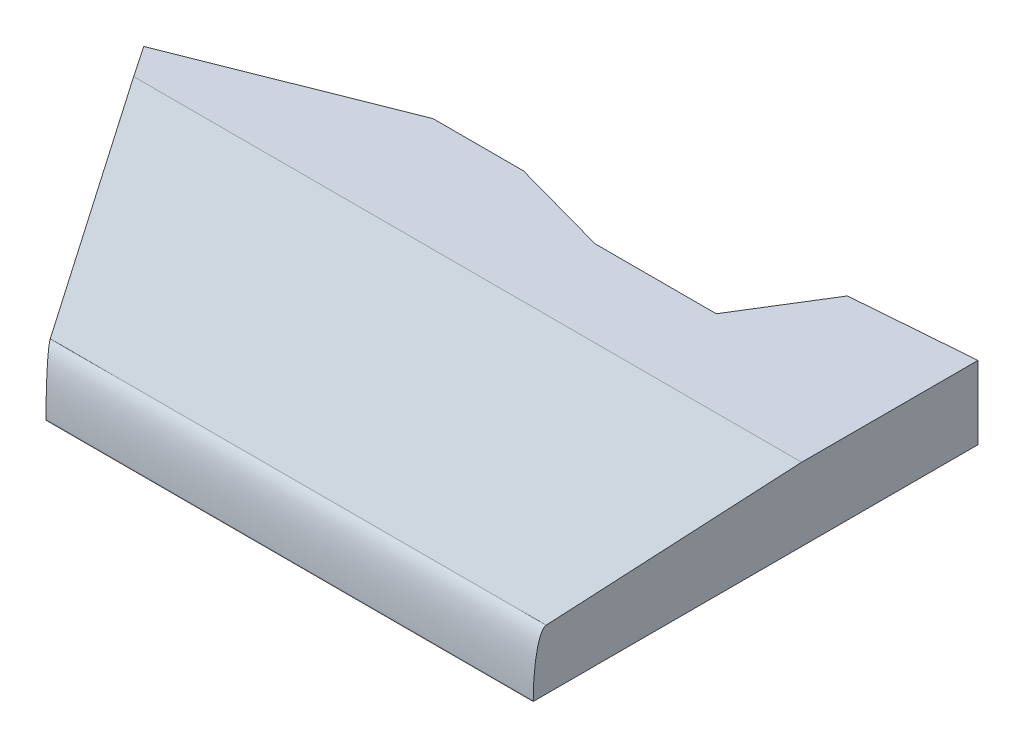
SolidWorks part; units mm, degrees
ref_plane "Front Plane" through (0, 0, 0) normal (0, 0, 1) x (1, 0, 0)
ref_plane "Top Plane" through (0, 0, 0) normal (0, 1, 0) x (1, 0, 0)
ref_plane "Right Plane" through (0, 0, 0) normal (1, 0, 0) x (0, 0, -1)
sketch "outline" plane through (0, 0, 0) normal (0, 1, 0) x (1, 0, 0)
  line L0 (23.1521, 111.8179) -> (23.1521, 32.6746) construction
  line L1 (23.1521, 32.6746) -> (26.0432, 26.4778) construction
  line L2 (26.0432, 26.4778) -> (40.0838, 2.1711) construction
  line L3 (40.0838, 2.1711) -> (75.1374, 16.0801) construction
  line L4 (75.1374, 16.0801) -> (93.8189, 16.0801) construction
  line L5 (93.8189, 16.0801) -> (112.2703, 10.9819) construction
  line L6 (112.2703, 10.9819) -> (130.9633, 10.9819) construction
  line L7 (130.9633, 10.9819) -> (140.1644, 25.8373) construction
  line L8 (140.1644, 25.8373) -> (160.3881, 27.4157) construction
  line L9 (160.3881, 27.4157) -> (160.3881, 105.6539) construction
  line L10 (160.3881, 105.6539) -> (121.5662, 111.8179) construction
  line L11 (121.5662, 111.8179) -> (23.1521, 111.8179) construction
  line L12 (22.7521, 112.2179) -> (22.7521, 32.5858)
  line L13 (22.7521, 32.5858) -> (25.6881, 26.2928)
  line L14 (25.6881, 26.2928) -> (39.9102, 1.6719)
  line L15 (39.9102, 1.6719) -> (75.2139, 15.6801)
  line L16 (75.2139, 15.6801) -> (93.7646, 15.6801)
  line L17 (93.7646, 15.6801) -> (112.216, 10.5819)
  line L18 (112.216, 10.5819) -> (131.1861, 10.5819)
  line L19 (131.1861, 10.5819) -> (140.3977, 25.4543)
  line L20 (140.3977, 25.4543) -> (160.7881, 27.0457)
  line L21 (160.7881, 27.0457) -> (160.7881, 105.9954)
  line L22 (160.7881, 105.9954) -> (121.5978, 112.2179)
  line L23 (121.5978, 112.2179) -> (22.7521, 112.2179)
  line L36 (23.9521, 111.0179) -> (23.9521, 32.852)
  line L37 (23.9521, 32.852) -> (26.7534, 26.8477)
  line L38 (26.7534, 26.8477) -> (40.431, 3.1695)
  line L39 (40.431, 3.1695) -> (74.9845, 16.8801)
  line L40 (74.9845, 16.8801) -> (93.9274, 16.8801)
  line L41 (93.9274, 16.8801) -> (112.3788, 11.7819)
  line L42 (112.3788, 11.7819) -> (130.5178, 11.7819)
  line L43 (130.5178, 11.7819) -> (139.6978, 26.6033)
  line L44 (139.6978, 26.6033) -> (159.5881, 28.1556)
  line L45 (159.5881, 28.1556) -> (159.5881, 104.9709)
  line L46 (159.5881, 104.9709) -> (121.5031, 111.0179)
  line L47 (121.5031, 111.0179) -> (23.9521, 111.0179)
  line L48 (17.5521, 117.4179) -> (17.5521, 31.4325)
  line L49 (17.5521, 31.4325) -> (21.0718, 23.8885)
  line L50 (21.0718, 23.8885) -> (37.6538, -4.8178)
  line L51 (37.6538, -4.8178) -> (76.2079, 10.4801)
  line L52 (76.2079, 10.4801) -> (93.0594, 10.4801)
  line L53 (93.0594, 10.4801) -> (111.5108, 5.3819)
  line L54 (111.5108, 5.3819) -> (134.0819, 5.3819)
  line L55 (134.0819, 5.3819) -> (143.4304, 20.4752)
  line L56 (143.4304, 20.4752) -> (165.9881, 22.2357)
  line L57 (165.9881, 22.2357) -> (165.9881, 110.4349)
  line L58 (165.9881, 110.4349) -> (122.008, 117.4179)
  line L59 (122.008, 117.4179) -> (17.5521, 117.4179)
  dimension "D1" = 137.236
  dimension "D3" = 5.2
  dimension "D4" = 1.2
  dimension "D2" = 0.4
sketch "wrist" plane through (0, 0, 0) normal (0, 1, 0) x (1, 0, 0)
  line L0 (165.9881, 22.2357) -> (165.9881, -60.6181)
  line L1 (165.9881, -60.6181) -> (75.2317, -60.6181)
  line L2 (75.2317, -60.6181) -> (37.6538, -4.8178)
  line L3 (37.6538, -4.8178) -> (76.2079, 10.4801)
  line L4 (76.2079, 10.4801) -> (93.0594, 10.4801)
  line L5 (93.0594, 10.4801) -> (111.5108, 5.3819)
  line L6 (111.5108, 5.3819) -> (134.0819, 5.3819)
  line L7 (134.0819, 5.3819) -> (143.4304, 20.4752)
  line L8 (143.4304, 20.4752) -> (165.9881, 22.2357)
  line L9 (37.6538, -4.8178) -> (165.9881, -4.8178)
  dimension "D1" = 66
extrude "Boss-Extrude1" add sketch "wrist" along normal blind 13.6 contours L3 L9 L0 L8 L7 L6 L5 L4 region at (116.7875, 0, -3.8943)
extrude "Boss-Extrude2" add sketch "wrist<5>" along normal blind 13.6 contours L9 L2 L1 L0 region at (110.6783, 0, 31.1229)
sketch "wrist<5>" plane through (0, 0, 0) normal (0, 1, 0) x (1, 0, 0) same geometry as "wrist"
chamfer "Chamfer1" distance 50 angle 3 1 edges at (120.6099, 13.6, 60.6181) first distance on face at (111.4613, 13.6, 5.7355)
fillet "Fillet1" radius 3 1 edges at (120.6099, 10.9796, 60.6181) second distance 11 first distance on face at (112.1919, 12.2898, 35.6181)
sketch "Sketch3" plane through (-0.72, 0, -9.2249) normal (-0.0778, 0, -0.997) x (-0.997, 0, 0.0778)
  line L0 (-167.215, 0) -> (-144.5887, 13.6) construction
  point P6 (-155.9018, 6.8)
sketch "Sketch4" plane through (0, 0, -5.3819) normal (0, 0, -1) x (-1, 0, 0)
  line L0 (-134.0819, 0) -> (-111.5108, 13.6) construction
  point P6 (-122.7964, 6.8)
sketch "Sketch5" plane through (0, 0, -10.4801) normal (0, 0, -1) x (-1, 0, 0)
  line L0 (-93.0594, 0) -> (-76.2079, 13.6) construction
  point P6 (-84.6336, 6.8)
hole_wizard "Ø3.0mm Dowel Hole1" positions "Sketch3" profile "Sketch6" hole size "Ø3.0" standard "ANSI Metric"
sketch "Sketch6" plane through (154.7092, 6.8, -21.3554) normal (0, 1, 0) x (-0.997, 0, 0.0778)
  line L0 (0, 0) -> (0, 1.2)
  line L1 (0, 1.2) -> (1.6, 1.2)
  line L2 (1.6, 1.2) -> (1.6, 0)
  line L5 (1.6, 0) -> (0, 0)
  line L10 (0, 1.2) -> (-1.6, 1.2) construction
  line L11 (0, -6.35) -> (0, 107.95) construction
  dimension "Hole Dia." = 3.2
  dimension "Hole Depth" = 1.2
  dimension "Drill Angle" = 180
hole_wizard "Ø3.0mm Dowel Hole2" positions "Sketch4" profile "Sketch7" hole size "Ø3.0" standard "ANSI Metric"
sketch "Sketch7" plane through (122.7964, 6.8, -5.3819) normal (1, 0, 0) x (0, 1, 0)
  line L0 (0, 0) -> (0, 1.2)
  line L1 (0, 1.2) -> (1.6, 1.2)
  line L2 (1.6, 1.2) -> (1.6, 0)
  line L5 (1.6, 0) -> (0, 0)
  line L10 (0, 1.2) -> (-1.6, 1.2) construction
  line L11 (0, -6.35) -> (0, 107.95) construction
  dimension "Hole Dia." = 3.2
  dimension "Hole Depth" = 1.2
  dimension "Drill Angle" = 180
hole_wizard "Ø3.0mm Dowel Hole3" positions "Sketch5" profile "Sketch8" hole size "Ø3.0" standard "ANSI Metric"
sketch "Sketch8" plane through (84.6336, 6.8, -10.4801) normal (1, 0, 0) x (0, 1, 0)
  line L0 (0, 0) -> (0, 1.2)
  line L1 (0, 1.2) -> (1.6, 1.2)
  line L2 (1.6, 1.2) -> (1.6, 0)
  line L5 (1.6, 0) -> (0, 0)
  line L10 (0, 1.2) -> (-1.6, 1.2) construction
  line L11 (0, -6.35) -> (0, 107.95) construction
  dimension "Hole Dia." = 3.2
  dimension "Hole Depth" = 1.2
  dimension "Drill Angle" = 180
mirror "Mirror1" [suppressed] of bodies 113
delete or keep bodies "Body-Delete/Keep 1" [suppressed] type delete bodies bodies 113
